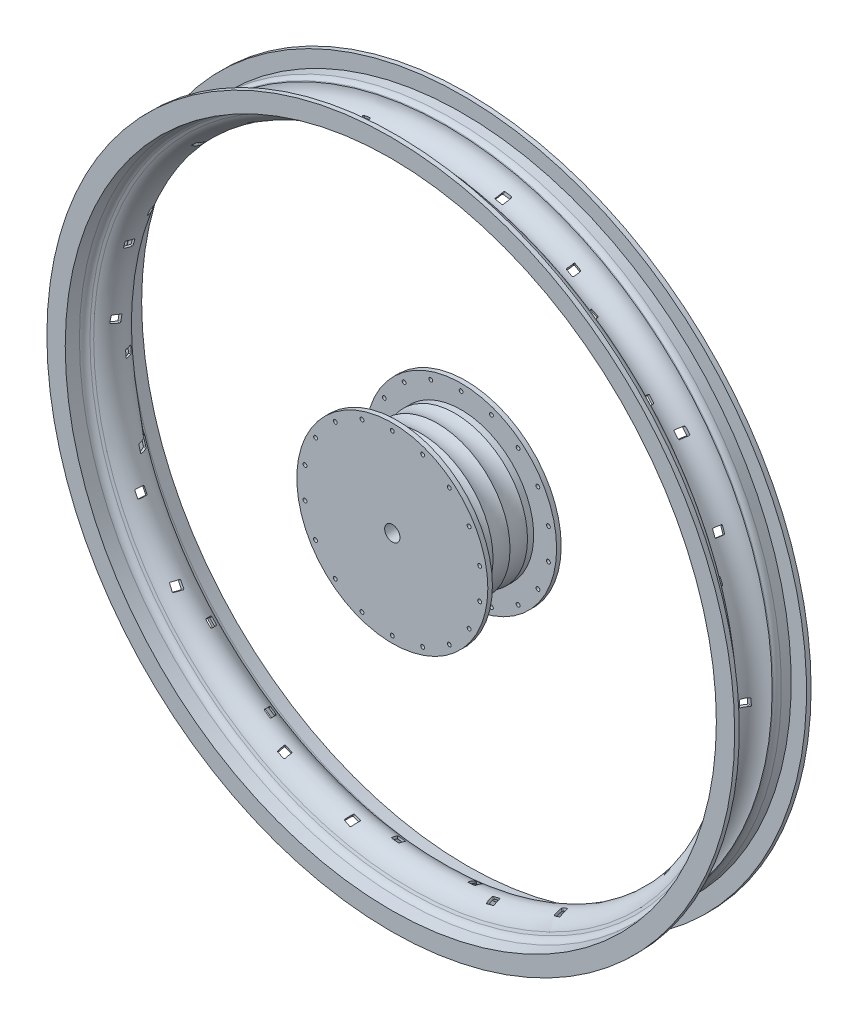
SolidWorks part; units mm, degrees
ref_plane "Спереди" through (0, 0, 0) normal (0, 0, 1) x (1, 0, 0)
ref_plane "Сверху" through (0, 0, 0) normal (0, 1, 0) x (1, 0, 0)
ref_plane "Справа" through (0, 0, 0) normal (1, 0, 0) x (0, 0, -1)
sketch "Эскиз1" plane through (0, 0, 0) normal (0, 0, 1) x (1, 0, 0)
  circle A0 centre (0, 0) radius 47.5
  dimension "D1" = 95
extrude "Бобышка-Вытянуть1" add sketch "Эскиз1" along normal mid plane 42
sketch "Эскиз3" plane through (0, 0, 0) normal (1, 0, 0) x (0, 0, -1)
  line L0 (-18.724, 0) -> (37.7483, 0) construction
  arc A0 (-5.5533, 47.4635) -> (5.5533, 47.4635) centre (0, 61.3977) ccw
  arc A1 (5.5533, 47.4635) -> (5.648, 75.2937) centre (11.2014, 61.3596) ccw
  arc A2 (-5.5533, 47.4635) -> (-5.648, 75.2937) centre (-11.2014, 61.3596) cw
  arc A3 (5.648, 75.2937) -> (-5.648, 75.2937) centre (0, 61.3977) ccw
  point P5 (5.5533, 47.4635)
  point P6 (5.5533, 47.4635)
  dimension "D1" = 30
  dimension "D2" = 30
revolve "Вырез-Повернуть1" cut sketch "Эскиз3" angle 360 about L0
sketch "Эскиз4" plane through (0, 0, 21) normal (0, 0, 1) x (1, 0, 0)
  circle A0 centre (0, 0) radius 5
  dimension "D1" = 10
extrude "Вырез-Вытянуть1" cut sketch "Эскиз4" against normal blind 42
sketch "Эскиз5" plane through (0, 0, 21) normal (0, 0, 1) x (1, 0, 0)
  circle A0 centre (0, 0) radius 62.5
  circle A1 centre (0, 0) radius 5
  dimension "D1" = 125
extrude "Бобышка-Вытянуть3" add sketch "Эскиз5" along normal blind 3
sketch "Эскиз8" plane through (0, 0, 24) normal (0, 0, 1) x (1, 0, 0)
  circle A0 centre (0, 58) radius 1.25
  circle A1 centre (19.8372, 54.5022) radius 1.25
  circle A2 centre (37.2817, 44.4306) radius 1.25
  circle A3 centre (50.2295, 29) radius 1.25
  circle A4 centre (57.1188, 10.0716) radius 1.25
  circle A5 centre (57.1188, -10.0716) radius 1.25
  circle A6 centre (50.2295, -29) radius 1.25
  circle A7 centre (37.2817, -44.4306) radius 1.25
  circle A8 centre (19.8372, -54.5022) radius 1.25
  circle A9 centre (0, -58) radius 1.25
  circle A10 centre (-19.8372, -54.5022) radius 1.25
  circle A11 centre (-37.2817, -44.4306) radius 1.25
  circle A12 centre (-50.2295, -29) radius 1.25
  circle A13 centre (-57.1188, -10.0716) radius 1.25
  circle A14 centre (-57.1188, 10.0716) radius 1.25
  circle A15 centre (-50.2295, 29) radius 1.25
  circle A16 centre (-37.2817, 44.4306) radius 1.25
  circle A17 centre (-19.8372, 54.5022) radius 1.25
  point P40 (0, 0)
  dimension "D1" = 2.5
  dimension "D2" = 58
  dimension "D3" = 18
extrude "Вырез-Вытянуть3" cut sketch "Эскиз8" against normal blind 3
mirror "Зеркальное отражение3" about plane through (0, 0, 0) normal (0, 0, 1) of "Вырез-Вытянуть3", "Бобышка-Вытянуть3"
sketch "Эскиз9" plane through (0, 0, 0) normal (0, 0, 1) x (1, 0, 0)
  circle A0 centre (0, 0) radius 225
  circle A1 centre (0, 0) radius 213
  dimension "D1" = 450
  dimension "D2" = 426
extrude "Бобышка-Вытянуть4" add sketch "Эскиз9" along normal mid plane 50 separate body
sketch "Эскиз10" plane through (0, 0, 0) normal (0, 1, 0) x (1, 0, 0)
  line L0 (0, 30.5135) -> (0, -30.7758) construction
  line L1 (-213, 25) -> (-213, -25)
  line L2 (-213, 25) -> (-212.1148, 16.5952)
  line L3 (-213, -25) -> (-212.1148, -16.5952)
  line L4 (-207.5655, -11.8096) -> (-209.2325, -12.5767)
  line L5 (-207.5655, 11.8096) -> (-209.2325, 12.5767)
  arc A0 (-207.5655, -11.8096) -> (-207.5655, 11.8096) centre (-213, 0) ccw
  arc A1 (-212.1148, 16.5952) -> (-209.2325, 12.5767) centre (-207.1423, 17.1188) ccw
  arc A2 (-212.1148, -16.5952) -> (-209.2325, -12.5767) centre (-207.1423, -17.1188) cw
  point P12 (-211.8169, 13.766)
  point P18 (-211.8169, -13.766)
  dimension "D2" = 5
revolve "Повернуть1" add sketch "Эскиз10" angle 360 about L0
sketch "Эскиз11" plane through (0, 0, 0) normal (0, 1, 0) x (1, 0, 0)
  line L0 (-225, 22) -> (-215, 22)
  line L1 (-225, 25) -> (-225, -25) construction
  line L2 (-215, 22) -> (-215, 15.5299)
  line L3 (-213.3625, 11.8294) -> (-213, 11.5)
  line L4 (-215, -22) -> (-215, -15.5299)
  line L5 (-225, -22) -> (-215, -22)
  line L6 (-225, 22) -> (-225, -22)
  line L7 (-213.3625, -11.8294) -> (-213, -11.5)
  line L8 (0, 37.1085) -> (0, -40.285) construction
  arc A0 (-213, -11.5) -> (-213, 11.5) centre (-213, 0) ccw
  arc A1 (-215, 15.5299) -> (-213.3625, 11.8294) centre (-210, 15.5299) ccw
  arc A2 (-213.3625, -11.8294) -> (-215, -15.5299) centre (-210, -15.5299) ccw
  dimension "D2" = 23
  dimension "D3" = 5
  dimension "D4" = 5
  dimension "D1" = 10
revolve "Вырез-Повернуть2" cut sketch "Эскиз11" angle 360 about L8
sketch "Эскиз12" plane through (0, 0, 24) normal (0, 0, 1) x (1, 0, 0)
  circle A0 centre (0, 58) radius 1.25
ref_plane "Плоскость1" through (0, 0, 4) normal (0, 0, 1) x (1, 0, 0)
sketch "Эскиз17" plane through (0, 0, 0) normal (1, 0, 0) x (0, 0, -1)
  line L0 (-27, 58) -> (25, 58) construction
  line L1 (-24, 59.25) -> (-24, 56.75) construction
  line L2 (25, -225) -> (25, 225) construction
  point P2 (-24, 58)
  point P8 (18, 58)
  dimension "D1" = 3
  dimension "D2" = 7
sketch "Эскиз18" plane through (0, 0, 4) normal (0, 0, 1) x (1, 0, 0)
  line L0 (0, 58) -> (-109.416, 167.416) construction
  line L1 (0, 58) -> (109.416, 167.416) construction
  circle A0 centre (0, 0) radius 200
sketch3d "Трехмерный эскиз2"
  line L2 (-109.416, 167.416, 4) -> (-58.6442, 116.6442, 14.6726)
  line L3 (109.416, 167.416, 4) -> (54.708, 112.708, -7)
ref_plane "Плоскость3" through (-58.6442, 116.6442, 14.6726) normal (0.6994, -0.6994, 0.147) x (0.104, -0.104, -0.9891)
sketch "Эскиз19" plane through (-58.6442, 116.6442, 14.6726) normal (0.6994, -0.6994, 0.147) x (0.104, -0.104, -0.9891)
  line L1 (-2, -2.5) -> (2, -2.5)
  line L2 (-2.5, -2) -> (-2.5, 2)
  line L3 (-2, 2.5) -> (2, 2.5)
  line L4 (2.5, -2) -> (2.5, 2)
  line L5 (-2.5, -2.5) -> (2.5, 2.5) construction
  line L6 (-2.5, 2.5) -> (2.5, -2.5) construction
  arc A0 (2, 2.5) -> (2.5, 2) centre (2, 2) cw
  arc A1 (2.5, -2) -> (2, -2.5) centre (2, -2) cw
  arc A2 (-2.5, -2) -> (-2, -2.5) centre (-2, -2) ccw
  arc A3 (-2.5, 2) -> (-2, 2.5) centre (-2, 2) cw
  point P0 (0, 0)
  dimension "D3" = 0.5
  dimension "D1" = 5
  dimension "D2" = 5
extrude "Вырез-Вытянуть5" cut sketch "Эскиз19" against normal blind 100
ref_plane "Плоскость4" through (54.708, 112.708, -7) normal (-0.7001, -0.7001, -0.1408) x (-0.7141, 0.6863, 0.138)
sketch "Эскиз20" plane through (54.708, 112.708, -7) normal (-0.7001, -0.7001, -0.1408) x (-0.7141, 0.6863, 0.138)
  line L1 (-2, -2.5) -> (2, -2.5)
  line L2 (-2.5, -2) -> (-2.5, 2)
  line L3 (-2, 2.5) -> (2, 2.5)
  line L4 (2.5, -2) -> (2.5, 2)
  line L5 (-2.5, -2.5) -> (2.5, 2.5) construction
  line L6 (-2.5, 2.5) -> (2.5, -2.5) construction
  arc A0 (2, 2.5) -> (2.5, 2) centre (2, 2) cw
  arc A1 (2.5, -2) -> (2, -2.5) centre (2, -2) cw
  arc A2 (-2, -2.5) -> (-2.5, -2) centre (-2, -2) cw
  arc A3 (-2.5, 2) -> (-2, 2.5) centre (-2, 2) cw
  point P0 (0, 0)
  dimension "D3" = 0.5
  dimension "D1" = 5
  dimension "D2" = 5
extrude "Вырез-Вытянуть6" cut sketch "Эскиз20" against normal blind 100
ref_plane "Плоскость5" through (0, 0, -4) normal (0, 0, 1) x (1, 0, 0)
sketch "Эскиз21" plane through (0, 0, -4) normal (0, 0, 1) x (1, 0, 0)
  line L2 (19.8372, 54.5022) -> (42.7212, 65.1732) construction
  line L3 (19.8372, 54.5022) -> (-25.6798, 152.1136) construction
  line L4 (-25.6798, 152.1136) -> (-45.5578, 194.7421) construction
  line L5 (42.7212, 65.1732) -> (158.5422, 121.9196) construction
  circle A0 centre (0, 0) radius 200
sketch "Эскиз22" plane through (0, 0, -24) normal (0, 0, -1) x (-1, 0, 0)
  circle A0 centre (-19.8372, 54.5022) radius 1.25
sketch "Эскиз23" plane through (0, 0, 0) normal (1, 0, 0) x (0, 0, -1)
  line L0 (27, 54.5022) -> (-25, 54.5022) construction
  line L1 (-25, 225) -> (-25, -225) construction
  line L2 (24, 53.2522) -> (24, 55.7522) construction
  point P4 (24, 54.5022)
  point P5 (-18, 54.5022)
  dimension "D1" = 3
  dimension "D2" = 7
ref_plane "Плоскость6" through (19.8372, 0, 0) normal (1, 0, 0) x (0, 0, -1)
sketch "Эскиз24" plane through (19.8372, 0, 0) normal (1, 0, 0) x (0, 0, -1)
  line L0 (-25, 54.5022) -> (27, 54.5022) construction
  point P4 (-18, 54.5022)
sketch3d "Трехмерный эскиз4"
  line L1 (-45.5578, 194.7421, -4) -> (-23.1125, 146.608, -11.8942)
  line L2 (158.5422, 121.9196, -4) -> (97.1574, 92.0836, 5.7362)
ref_plane "Плоскость7" through (97.1574, 92.0836, 5.7362) normal (-0.8904, -0.4328, 0.1412) x (0.127, 0.0617, 0.99)
sketch "Эскиз25" plane through (97.1574, 92.0836, 5.7362) normal (-0.8904, -0.4328, 0.1412) x (0.127, 0.0617, 0.99)
  line L1 (-2, -2.5) -> (2, -2.5)
  line L2 (-2.5, -2) -> (-2.5, 2)
  line L3 (-2, 2.5) -> (2, 2.5)
  line L4 (2.5, -2) -> (2.5, 2)
  line L5 (-2.5, -2.5) -> (2.5, 2.5) construction
  line L6 (-2.5, 2.5) -> (2.5, -2.5) construction
  arc A0 (2, 2.5) -> (2.5, 2) centre (2, 2) cw
  arc A1 (2.5, -2) -> (2, -2.5) centre (2, -2) cw
  arc A2 (-2, -2.5) -> (-2.5, -2) centre (-2, -2) cw
  arc A3 (-2.5, 2) -> (-2, 2.5) centre (-2, 2) cw
  point P0 (0, 0)
  dimension "D3" = 0.5
  dimension "D1" = 5
  dimension "D2" = 5
extrude "Вырез-Вытянуть7" cut sketch "Эскиз25" against normal blind 97
ref_plane "Плоскость8" through (-23.1125, 146.608, -11.8942) normal (0.418, -0.8965, -0.147) x (-0.9084, -0.4125, -0.0677)
sketch "Эскиз26" plane through (-23.1125, 146.608, -11.8942) normal (0.418, -0.8965, -0.147) x (-0.9084, -0.4125, -0.0677)
  line L1 (-2, -2.5) -> (2, -2.5)
  line L2 (-2.5, -2) -> (-2.5, 2)
  line L3 (-2, 2.5) -> (2, 2.5)
  line L4 (2.5, -2) -> (2.5, 2)
  line L5 (-2.5, -2.5) -> (2.5, 2.5) construction
  line L6 (-2.5, 2.5) -> (2.5, -2.5) construction
  arc A0 (2, 2.5) -> (2.5, 2) centre (2, 2) cw
  arc A1 (2.5, -2) -> (2, -2.5) centre (2, -2) cw
  arc A2 (-2, -2.5) -> (-2.5, -2) centre (-2, -2) cw
  arc A3 (-2.5, 2) -> (-2, 2.5) centre (-2, 2) cw
  point P0 (0, 0)
  dimension "D3" = 0.5
  dimension "D1" = 5
  dimension "D2" = 5
extrude "Вырез-Вытянуть8" cut sketch "Эскиз26" against normal blind 97
pattern_circular "Круговой массив1" count 9 every 40 about axis through (0, 0, -21) along (0, 0, 1) of "Вырез-Вытянуть5", "Вырез-Вытянуть6", "Вырез-Вытянуть7", "Вырез-Вытянуть8"
